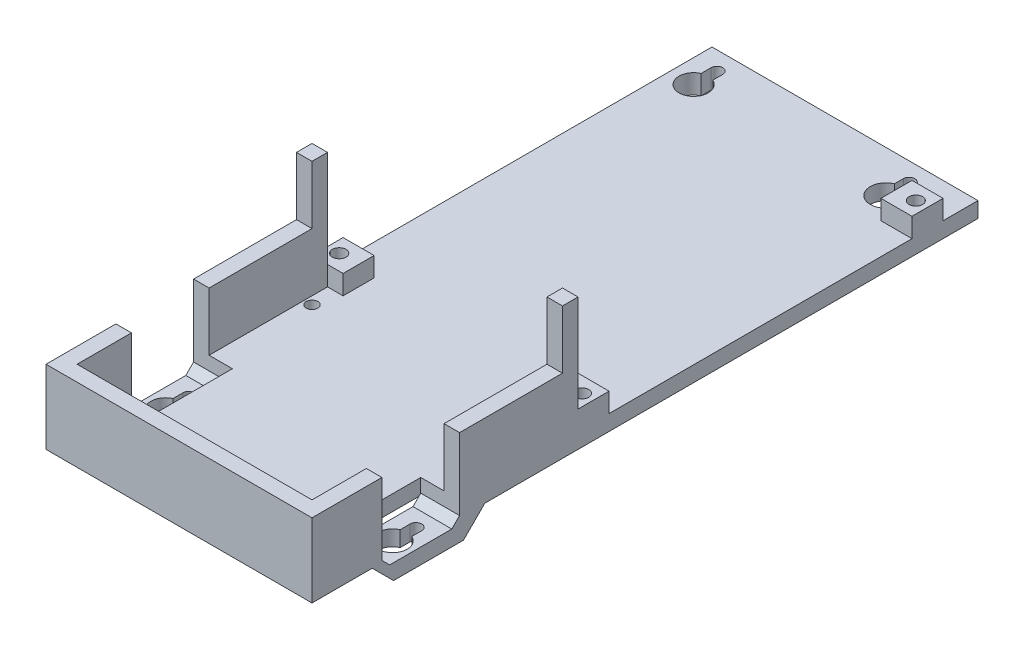
SolidWorks part; units mm, degrees
ref_plane "Front Plane" through (0, 0, 0) normal (0, 0, 1) x (1, 0, 0)
ref_plane "Top Plane" through (0, 0, 0) normal (0, 1, 0) x (1, 0, 0)
ref_plane "Right Plane" through (0, 0, 0) normal (1, 0, 0) x (0, 0, -1)
sketch "Sketch1" plane through (0, 0, 0) normal (0, 1, 0) x (1, 0, 0)
  line L1 (0, 0) -> (-68.5, 0)
  line L2 (0, 0) -> (0, 64.5)
  line L3 (0, 64.5) -> (-68.5, 64.5)
  line L4 (-68.5, 0) -> (-68.5, 64.5)
  dimension "D1" = 64.5
  dimension "D2" = 68.5
extrude "Boss-Extrude3" add sketch "Sketch1" along normal blind 19
sketch "Sketch3" plane through (0, 19, 0) normal (0, 1, 0) x (1, 0, 0)
  line L0 (0, 64.5) -> (-68.5, 64.5) construction
  line L1 (-64.5, 64.5) -> (-4, 64.5)
  line L2 (-64.5, 64.5) -> (-64.5, 4)
  line L3 (-64.5, 4) -> (-4, 4)
  line L4 (-4, 64.5) -> (-4, 4)
  line L5 (-68.5, 64.5) -> (-68.5, 0) construction
  line L6 (-68.5, 0) -> (0, 0) construction
  line L7 (0, 0) -> (0, 64.5) construction
  dimension "D1" = 4
  dimension "D2" = 4
  dimension "D3" = 4
extrude "Cut-Extrude1" cut sketch "Sketch3" against normal blind 15
sketch "Sketch5" plane through (0, 0, -64.5) normal (0, 0, -1) x (-1, 0, 0)
  line L0 (68.5, 19) -> (68.5, 0) construction
  line L1 (0, 0) -> (68.5, 0)
  line L2 (0, 0) -> (0, 4)
  line L3 (0, 4) -> (68.5, 4)
  line L4 (68.5, 0) -> (68.5, 4)
extrude "Boss-Extrude4" add sketch "Sketch5" along normal blind 105
sketch "Sketch9" plane through (0, 19, 0) normal (0, 1, 0) x (1, 0, 0)
  line L0 (-4, 4) -> (-4, 64.5) construction
  line L1 (-4, 38) -> (0, 38)
  line L2 (-4, 38) -> (-4, 18)
  line L3 (-4, 18) -> (0, 18)
  line L4 (0, 38) -> (0, 18)
  line L5 (0, 0) -> (0, 64.5) construction
  line L6 (-4, 64.5) -> (0, 64.5) construction
  dimension "D1" = 20
  dimension "D2" = 26.5
sketch "Sketch10" plane through (0, 0, 0) normal (0, -1, 0) x (1, 0, 0)
  line L0 (0, 0) -> (0, -169.5) construction
  line L1 (0, -15.5) -> (-10, -15.5)
  line L2 (0, -15.5) -> (0, -44.5)
  line L3 (0, -44.5) -> (-10, -44.5)
  line L4 (-10, -15.5) -> (-10, -44.5)
  line L5 (-68.5, 0) -> (0, 0) construction
  dimension "D1" = 15.5
  dimension "D2" = 10
  dimension "D3" = 29
extrude "Boss-Extrude5" add sketch "Sketch10" along normal blind 5.5
extrude "Cut-Extrude2" cut sketch "Sketch9" against normal blind 20.5
sketch "Sketch11" plane through (0, 4, 0) normal (0, 1, 0) x (1, 0, 0)
  line L1 (-4, 38) -> (-10, 38)
  line L2 (-4, 38) -> (-4, 18)
  line L3 (-4, 18) -> (-10, 18)
  line L4 (-10, 38) -> (-10, 18)
  dimension "D1" = 20
  dimension "4" = 6
extrude "Cut-Extrude3" cut sketch "Sketch11" against normal blind 5.5
chamfer "Chamfer2" distance 5.5 distance2 5.5 2 edges at (-5, -5.5, -44.5) (-5, -5.5, -15.5)
chamfer "Chamfer3" distance 2 angle 45 2 edges at (-5, -1.5, -38) (-5, -1.5, -18)
sketch "Sketch12" plane through (0, 19, 0) normal (0, 1, 0) x (1, 0, 0)
  line L1 (-68.5, 0) -> (-34.25, 0)
  line L2 (-68.5, 0) -> (-68.5, 169.5)
  line L3 (-68.5, 169.5) -> (-34.25, 169.5)
  line L4 (-34.25, 0) -> (-34.25, 169.5)
  dimension "D1" = 169.5
  dimension "D2" = 34.25
extrude "Cut-Extrude4" cut sketch "Sketch12" against normal blind 50
sketch "Sketch15" plane through (0, -1.5, 0) normal (0, 1, 0) x (1, 0, 0)
  line L0 (0, 20) -> (0, 36) construction
  line L1 (0, 36) -> (-10, 36) construction
  circle A0 centre (-5, 31.7571) radius 1.5
  dimension "D1" = 5
  dimension "D2" = 3
  dimension "D3" = 4.2429
extrude "Cut-Extrude5" cut sketch "Sketch15" against normal blind 50
sketch "Sketch16" plane through (0, 4, 0) normal (0, 1, 0) x (1, 0, 0)
  line L0 (-34.25, 4) -> (-4, 4) construction
  line L1 (-4, 4) -> (-4, 18) construction
  circle A0 centre (-6, 6) radius 1.5
  dimension "D3" = 3
  dimension "D1" = 2
  dimension "D2" = 2
extrude "Cut-Extrude6" cut sketch "Sketch16" against normal blind 50
sketch "Sketch17" plane through (0, 4, 0) normal (0, 1, 0) x (1, 0, 0)
  line L0 (-4, 38) -> (-4, 64.5) construction
  line L1 (-34.25, 4) -> (-4, 4) construction
  circle A0 centre (-6, 62.5) radius 1.5
  dimension "D2" = 3
  dimension "D3" = 58.5
  dimension "D1" = 2
extrude "Cut-Extrude7" cut sketch "Sketch17" against normal blind 50
sketch "Sketch19" plane through (0, 0, -169.5) normal (0, 0, -1) x (-1, 0, 0)
  line L1 (0, 4) -> (34.25, 4)
  line L2 (0, 4) -> (0, 0)
  line L3 (0, 0) -> (34.25, 0)
  line L4 (34.25, 4) -> (34.25, 0)
extrude "Boss-Extrude6" add sketch "Sketch19" along normal blind 2
sketch "Sketch26" plane through (0, 4, 0) normal (0, 1, 0) x (1, 0, 0)
  line L1 (0, 64.5) -> (-4, 64.5)
  line L2 (0, 64.5) -> (0, 68.5)
  line L3 (0, 68.5) -> (-4, 68.5)
  line L4 (-4, 64.5) -> (-4, 68.5)
  dimension "D1" = 4
  dimension "D2" = 4
extrude "Boss-Extrude7" add sketch "Sketch26" along normal blind 30
sketch "Sketch20" plane through (0, -1.5, 0) normal (0, 1, 0) x (1, 0, 0)
  line L0 (0, 20) -> (0, 36) construction
  circle A0 centre (-5, 25.7571) radius 3.75
  circle A2 centre (-5, 31.7571) radius 1.5 construction
  dimension "D1" = 5
  dimension "D2" = 7.5
  dimension "D3" = 6
extrude "Cut-Extrude9" cut sketch "Sketch20" against normal through all
sketch "Sketch21" plane through (0, -1.5, 0) normal (0, 1, 0) x (1, 0, 0)
  line L1 (-6.5, 31.7571) -> (-3.5, 31.7571)
  line L2 (-6.5, 31.7571) -> (-6.5, 29.1941)
  line L3 (-6.5, 29.1941) -> (-3.5, 29.1941)
  line L4 (-3.5, 31.7571) -> (-3.5, 29.1941)
  circle A0 centre (-5, 31.7571) radius 1.5 construction
  circle A1 centre (-5, 25.7571) radius 3.75 construction
  dimension "D1" = 2.5631
extrude "Cut-Extrude10" cut sketch "Sketch21" against normal blind 5
sketch "Sketch18" plane through (0, 4, 0) normal (0, 1, 0) x (1, 0, 0)
  line L0 (0, 171.5) -> (0, 68.5) construction
  circle A0 centre (-13, 166.7571) radius 1.5
  circle A1 centre (-5, 31.7571) radius 1.5 construction
  dimension "D1" = 135
  dimension "D2" = 3
  dimension "D3" = 13
extrude "Cut-Extrude8" cut sketch "Sketch18" against normal blind 135
sketch "Sketch24" plane through (0, 4, 0) normal (0, 1, 0) x (1, 0, 0)
  circle A0 centre (-13, 160.7571) radius 4
  circle A1 centre (-13, 166.7571) radius 1.5 construction
  circle A2 centre (-13, 166.7571) radius 1.5
  dimension "D2" = 8
  dimension "D1" = 6
extrude "Cut-Extrude13" cut sketch "Sketch24" against normal through all contours A0
sketch "Sketch25" plane through (0, 4, 0) normal (0, 1, 0) x (1, 0, 0)
  line L1 (-14.5, 166.7571) -> (-11.5, 166.7571)
  line L2 (-14.5, 166.7571) -> (-14.5, 164.4652)
  line L3 (-14.5, 164.4652) -> (-11.5, 164.4652)
  line L4 (-11.5, 166.7571) -> (-11.5, 164.4652)
  circle A0 centre (-13, 166.7571) radius 1.5 construction
  circle A1 centre (-13, 160.7571) radius 4 construction
extrude "Cut-Extrude14" cut sketch "Sketch25" against normal blind 5
sketch "Sketch27" plane through (0, 4, 0) normal (0, 1, 0) x (1, 0, 0)
  line L0 (0, 68.5) -> (-4, 68.5) construction
  line L1 (0, 171.5) -> (0, 68.5) construction
  circle A0 centre (-3, 72.5) radius 1.75
  circle A1 centre (-3, 158.5) radius 1.75
  dimension "D1" = 3.5
  dimension "D3" = 3
  dimension "D4" = 3.5
  dimension "D6" = 3
  dimension "D2" = 4
  dimension "D5" = 86
extrude "Cut-Extrude15" cut sketch "Sketch27" against normal through all
sketch "Sketch30" plane through (0, 4, 0) normal (0, 1, 0) x (1, 0, 0)
  line L0 (0, 68.5) -> (-4, 68.5) construction
  line L1 (0, 68.5) -> (-8, 68.5)
  line L2 (0, 68.5) -> (0, 76.5)
  line L3 (0, 76.5) -> (-8, 76.5)
  line L4 (-8, 68.5) -> (-8, 76.5)
  line L5 (0, 171.5) -> (0, 68.5) construction
  line L7 (0, 154.5) -> (-8, 154.5)
  line L8 (0, 154.5) -> (0, 162.5)
  line L9 (0, 162.5) -> (-8, 162.5)
  line L10 (-8, 154.5) -> (-8, 162.5)
  circle A1 centre (-3, 158.5) radius 1.75 construction
  circle A2 centre (-3, 158.5) radius 1.75
  circle A3 centre (-3, 72.5) radius 1.75
  dimension "D4" = 8
  dimension "D6" = 3.5
  dimension "D7" = 3.5
  dimension "D1" = 8
  dimension "D2" = 8
  dimension "D3" = 8
  dimension "D5" = 4
extrude "Boss-Extrude9" add sketch "Sketch30" along normal blind 5
ref_plane "Plane1" through (-34.25, 0, 0) normal (1, 0, 0) x (0, 0, -1)
mirror "Mirror5" about plane through (-34.25, 0, 0) normal (1, 0, 0) of bodies 125
sketch "Sketch31" plane through (0, 9, 0) normal (0, 1, 0) x (1, 0, 0)
  line L1 (-60.5, 154.5) -> (-68.5, 154.5)
  line L2 (-60.5, 154.5) -> (-60.5, 162.5)
  line L3 (-60.5, 162.5) -> (-68.5, 162.5)
  line L4 (-68.5, 154.5) -> (-68.5, 162.5)
extrude "Cut-Extrude16" cut sketch "Sketch31" against normal blind 5
sketch "Sketch32" plane through (0, 4, 0) normal (0, 1, 0) x (1, 0, 0)
  line L1 (-68.5, 171.5) -> (-48.7945, 171.5)
  line L2 (-68.5, 171.5) -> (-68.5, 154.2424)
  line L3 (-68.5, 154.2424) -> (-48.7945, 154.2424)
  line L4 (-48.7945, 171.5) -> (-48.7945, 154.2424)
extrude "Boss-Extrude10" add sketch "Sketch32" against normal blind 5
sketch "Sketch33" plane through (0, 4, 0) normal (0, 1, 0) x (1, 0, 0)
  line L0 (-68.5, 171.5) -> (-68.5, 76.5) construction
  line L1 (-68.5, 171.5) -> (0, 171.5) construction
  circle A0 centre (-62.5, 166.76) radius 1.5
  dimension "D2" = 3
  dimension "D1" = 6
  dimension "D3" = 4.74
extrude "Cut-Extrude17" cut sketch "Sketch33" against normal blind 5
sketch "Sketch34" plane through (0, 4, 0) normal (0, 1, 0) x (1, 0, 0)
  line L0 (-68.5, 171.5) -> (-68.5, 76.5) construction
  circle A0 centre (-62.5, 160.76) radius 3.75
  circle A1 centre (-62.5, 166.76) radius 1.5 construction
  dimension "D1" = 6
  dimension "7.5" = 7.5
  dimension "D2" = 6
extrude "Cut-Extrude18" cut sketch "Sketch34" against normal blind 5
sketch "Sketch35" plane through (0, 4, 0) normal (0, 1, 0) x (1, 0, 0)
  line L1 (-64, 166.76) -> (-61, 166.76)
  line L2 (-64, 166.76) -> (-64, 164.1969)
  line L3 (-64, 164.1969) -> (-61, 164.1969)
  line L4 (-61, 166.76) -> (-61, 164.1969)
  circle A0 centre (-62.5, 166.76) radius 1.5 construction
  circle A1 centre (-62.5, 160.76) radius 3.75 construction
extrude "Cut-Extrude19" cut sketch "Sketch35" against normal blind 5
equation "\"5.5.00mm\"=15"
